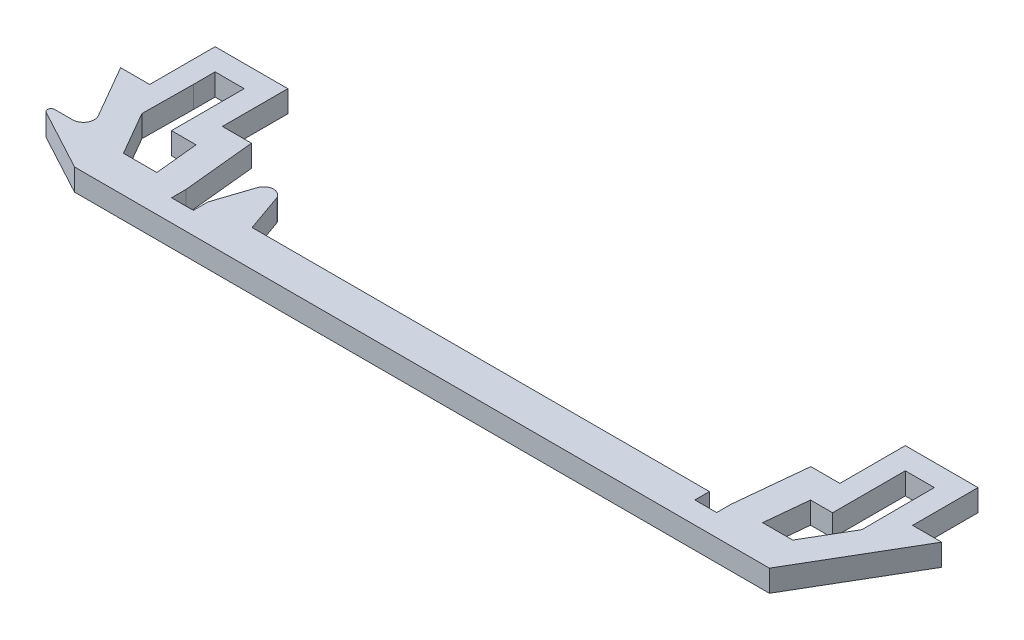
SolidWorks part; units mm, degrees
material "Custom Plastic"
ref_plane "Front Plane" through (0, 0, 0) normal (0, 0, 1) x (1, 0, 0)
ref_plane "Top Plane" through (0, 0, 0) normal (0, 1, 0) x (1, 0, 0)
ref_plane "Right Plane" through (0, 0, 0) normal (1, 0, 0) x (0, 0, -1)
sketch "Sketch1" plane through (0, 0, 0) normal (0, 1, 0) x (1, 0, 0)
  line L0 (-62.4186, -47.1587) -> (-58.4186, -47.1587)
  line L1 (-58.4186, -47.1587) -> (-58.4186, -38.1587)
  line L2 (-58.4186, -38.1587) -> (-48.4186, -38.1587)
  line L3 (-48.4186, -38.1587) -> (-48.4186, -47.1587)
  line L4 (-48.4186, -47.1587) -> (-44.4186, -47.1587)
  line L5 (-44.4186, -47.1587) -> (-43.4188, -57.1562)
  line L7 (31.5814, -57.2088) -> (32.5814, -47.2113)
  line L8 (32.5814, -47.2113) -> (36.5814, -47.2113)
  line L9 (36.5814, -47.2113) -> (36.5814, -38.2113)
  line L10 (36.5814, -38.2113) -> (46.5814, -38.2113)
  line L11 (46.5814, -38.2113) -> (46.5814, -47.2113)
  line L12 (46.5814, -47.2113) -> (50.5814, -47.2113)
  line L13 (50.5814, -47.2113) -> (41.8306, -62.1587)
  line L14 (41.8306, -62.1587) -> (-53.7583, -62.1587)
  line L15 (-58.2259, -54.4205) -> (-62.4186, -47.1587)
  line L16 (36.5478, -51.2113) -> (39.5814, -51.2113)
  line L17 (-55.4186, -41.1587) -> (-51.4186, -41.1587)
  line L18 (-55.4186, -41.1587) -> (-55.4186, -44.1587)
  line L20 (-51.4186, -41.1587) -> (-51.4186, -44.1587)
  line L21 (39.5814, -41.2113) -> (43.5814, -41.2113)
  line L22 (39.5814, -41.2113) -> (39.5814, -44.2113)
  line L24 (43.5814, -41.2113) -> (43.5814, -44.2113)
  line L25 (43.6046, -51.2113) -> (40.0934, -57.2088)
  line L26 (40.0934, -57.2088) -> (35.9479, -57.2088)
  line L27 (35.9479, -57.2088) -> (36.5478, -51.2113)
  line L28 (-51.4186, -51.1587) -> (-48.0385, -51.1587)
  line L29 (-48.0385, -51.1587) -> (-47.4385, -57.1587)
  line L30 (-47.4385, -57.1587) -> (-52.0263, -57.1587)
  line L31 (-52.0263, -57.1587) -> (-55.4904, -51.1587)
  line L32 (28.5814, -57.1587) -> (28.5814, -59.1587)
  line L33 (28.5814, -47.1587) -> (28.5814, -62.1587) construction
  line L34 (28.5814, -59.1587) -> (31.5814, -59.1587)
  line L35 (31.5814, -59.1587) -> (31.5814, -57.2088)
  line L36 (31.5814, -62.1587) -> (31.5814, -47.1587) construction
  line L38 (-43.4188, -57.1562) -> (-43.4188, -59.1587)
  line L39 (-43.4188, -59.1587) -> (-40.4188, -59.1587)
  line L40 (-40.4188, -59.1587) -> (-40.4188, -57.1587)
  line L41 (-34.3352, -57.1587) -> (28.5814, -57.1587)
  line L42 (-34.3352, -57.1587) -> (-36.1291, -52.0241)
  line L43 (43.5814, -44.2113) -> (43.6046, -51.2113)
  line L44 (-38.7227, -52.0447) -> (-40.4188, -57.1587)
  line L45 (39.5814, -44.2113) -> (39.5814, -51.2113)
  line L46 (-55.4186, -44.1587) -> (-55.4904, -51.1587)
  line L47 (-51.4186, -44.1587) -> (-51.4186, -51.1587)
  line L48 (-53.7583, -62.1587) -> (-62.2024, -57.6107)
  line L49 (-61.9653, -56.6705) -> (-59.525, -56.6705)
  arc A0 (-38.7227, -52.0447) -> (-36.1291, -52.0241) centre (-37.4224, -52.4759) cw
  arc A1 (-59.525, -56.6705) -> (-58.2259, -54.4205) centre (-59.525, -55.1705) ccw
  arc A2 (-62.2024, -57.6107) -> (-61.9653, -56.6705) centre (-61.9653, -57.1705) cw
  point P36 (-62.2024, -57.6107)
  point P56 (0, 0)
  point P57 (0, 0)
  point P58 (28.5814, -59.7154)
  point P59 (0, 0)
  dimension "D6" = 0.5
  dimension "D5" = 1.5
  dimension "D1" = 15
  dimension "D2" = 4
  dimension "D3" = 9
  dimension "D4" = 3
  dimension "D7" = 120
  dimension "D8" = 10
  dimension "D9" = 85
  dimension "D10" = 3
  dimension "D11" = 95.5889
  dimension "D12" = 3
  dimension "D13" = 3
  dimension "D14" = 3
  dimension "D15" = 3
  dimension "D17" = 4
  dimension "D18" = 4
  dimension "D19" = 4
  dimension "D20" = 4
  dimension "D21" = 4
  dimension "D23" = 2
  dimension "D24" = 3
extrude "Boss-Extrude1" add sketch "Sketch1" along normal blind 3
